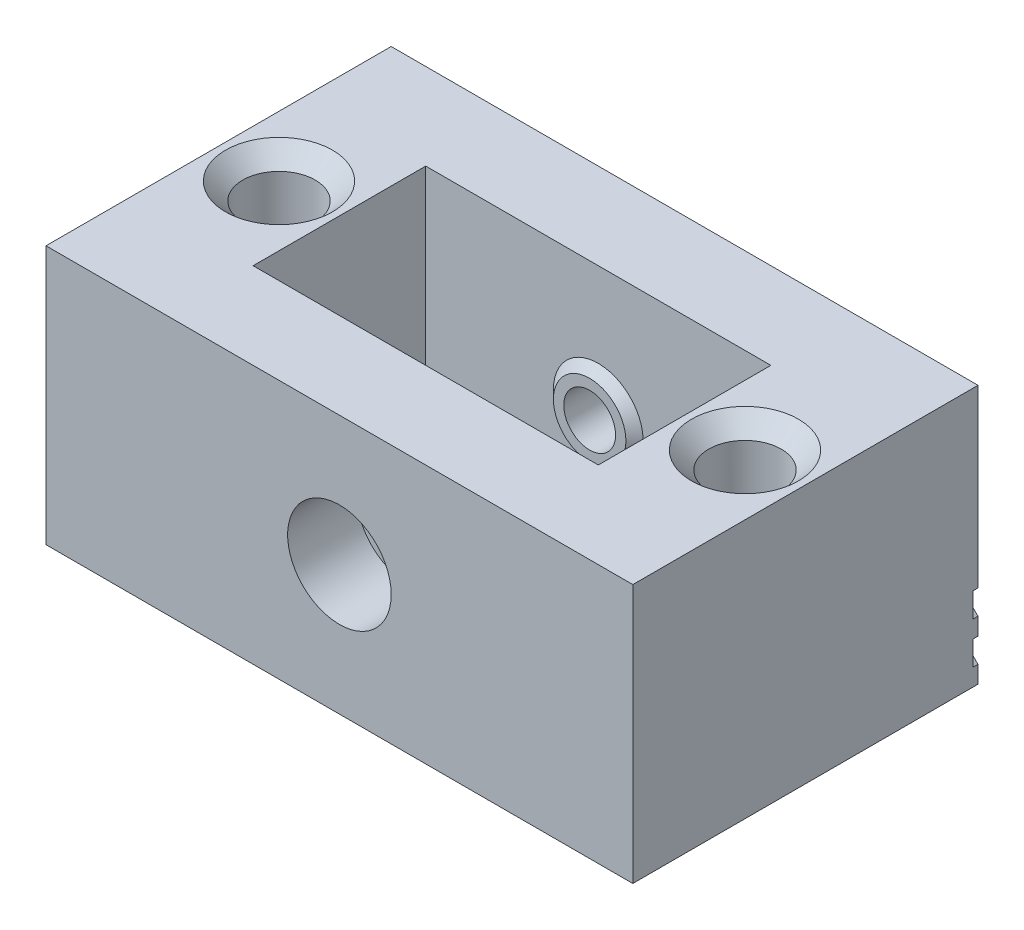
SolidWorks part; units mm, degrees
ref_plane "Front Plane" through (0, 0, 0) normal (0, 0, 1) x (1, 0, 0)
ref_plane "Top Plane" through (0, 0, 0) normal (0, 1, 0) x (1, 0, 0)
ref_plane "Right Plane" through (0, 0, 0) normal (1, 0, 0) x (0, 0, -1)
sketch "Sketch1" plane through (0, 0, 0) normal (0, 1, 0) x (1, 0, 0)
  line L1 (-17, -10) -> (17, -10)
  line L2 (-17, -10) -> (-17, 10)
  line L3 (-17, 10) -> (17, 10)
  line L4 (17, -10) -> (17, 10)
  line L5 (-17, -10) -> (17, 10) construction
  line L6 (-17, 10) -> (17, -10) construction
  point P0 (0, 0)
  dimension "D1" = 34
  dimension "D2" = 20
extrude "Boss-Extrude1" add sketch "Sketch1" along normal blind 15
sketch "Sketch3" plane through (0, 15, 0) normal (0, 1, 0) x (1, 0, 0)
  line L0 (-17, 10) -> (-17, -10) construction
  line L1 (-10, -5) -> (10, -5)
  line L2 (-10, -5) -> (-10, 5)
  line L3 (-10, 5) -> (10, 5)
  line L4 (10, -5) -> (10, 5)
  line L5 (17, -10) -> (17, 10) construction
  line L6 (-17, -10) -> (17, -10) construction
  dimension "D1" = 7
  dimension "D2" = 7
  dimension "D3" = 5
  dimension "D4" = 10
extrude "Cut-Extrude1" cut sketch "Sketch3" against normal blind 20
sketch "Sketch8" plane through (0, 0, -10) normal (0, 0, -1) x (-1, 0, 0)
  line L0 (-17, 7.5) -> (17, 7.5) construction
  line L1 (17, 15) -> (17, 0) construction
  line L2 (-17, 15) -> (-17, 0) construction
  circle A0 centre (0, 7.5) radius 1.5
  dimension "D1" = 3
extrude "Cut-Extrude6" cut sketch "Sketch8" against normal through all
sketch "Sketch9" plane through (0, 0, 10) normal (0, 0, 1) x (1, 0, 0)
  circle A0 centre (0, 7.5) radius 3
  dimension "D1" = 6
extrude "Cut-Extrude7" cut sketch "Sketch9" against normal blind 4
sketch "Sketch11" plane through (0, 0, -5) normal (0, 0, 1) x (1, 0, 0)
  circle A0 centre (0, 7.5) radius 2.1
  circle A1 centre (0, 7.5) radius 1.5
  dimension "D1" = 0.6
extrude "Boss-Extrude2" add sketch "Sketch11" along normal blind 0.5
sketch "Sketch12" plane through (0, 0, 5) normal (0, 0, -1) x (-1, 0, 0)
  circle A0 centre (0, 7.5) radius 2.1
  circle A1 centre (0, 7.5) radius 1.5
  dimension "D1" = 0.6
extrude "Boss-Extrude3" add sketch "Sketch12" along normal blind 0.5
chamfer "Chamfer5" distance 0.5 angle 45 2 edges at (-2.1, 7.5, -5) (2.1, 7.5, 5)
sketch "Sketch13" plane through (0, 15, 0) normal (0, 1, 0) x (1, 0, 0)
  line L0 (-17, 0) -> (17, 0) construction
  line L1 (-17, 10) -> (-17, -10) construction
  line L2 (17, -10) -> (17, 10) construction
  circle A0 centre (-13.5, 0) radius 2.1
  circle A1 centre (13.5, 0) radius 2.1
  dimension "D1" = 4.2
  dimension "D2" = 3.5
  dimension "D3" = 3.5
extrude "Cut-Extrude8" cut sketch "Sketch13" against normal through all
chamfer "Chamfer6" distance 1 angle 45 2 edges at (13.5, 15, 2.1) (-13.5, 15, 2.1)
sketch "Sketch14" plane through (0, 0, -10) normal (0, 0, -1) x (-1, 0, 0)
  line L0 (17, 3.4142) -> (17, 4.8284)
  line L5 (16.2929, 4.1213) -> (17, 3.4142)
  line L6 (17, 4.8284) -> (16.2929, 4.1213)
  line L7 (-17, 2.4142) -> (-16.2929, 1.7071)
  line L12 (-17, 15) -> (-17, 0) construction
  line L13 (-16.2929, 1.7071) -> (-17, 1)
  line L14 (-17, 1) -> (-17, 2.4142)
  line L15 (-17, 0) -> (17, 0) construction
  line L16 (0, 15) -> (0, 0) construction
  line L17 (-17, 15) -> (17, 15) construction
  line L18 (16.2929, 1.7071) -> (17, 1)
  line L19 (17, 1) -> (17, 2.4142)
  line L20 (17, 2.4142) -> (16.2929, 1.7071)
  line L21 (-17, 4.8284) -> (-16.2929, 4.1213)
  line L22 (-16.2929, 4.1213) -> (-17, 3.4142)
  line L23 (-17, 3.4142) -> (-17, 4.8284)
  dimension "D1" = 45
  dimension "D2" = 1
  dimension "D3" = 1
  dimension "D4" = 1
  dimension "D5" = 1
  dimension "D6" = 45
extrude "Cut-Extrude9" cut sketch "Sketch14" against normal blind 0.3
